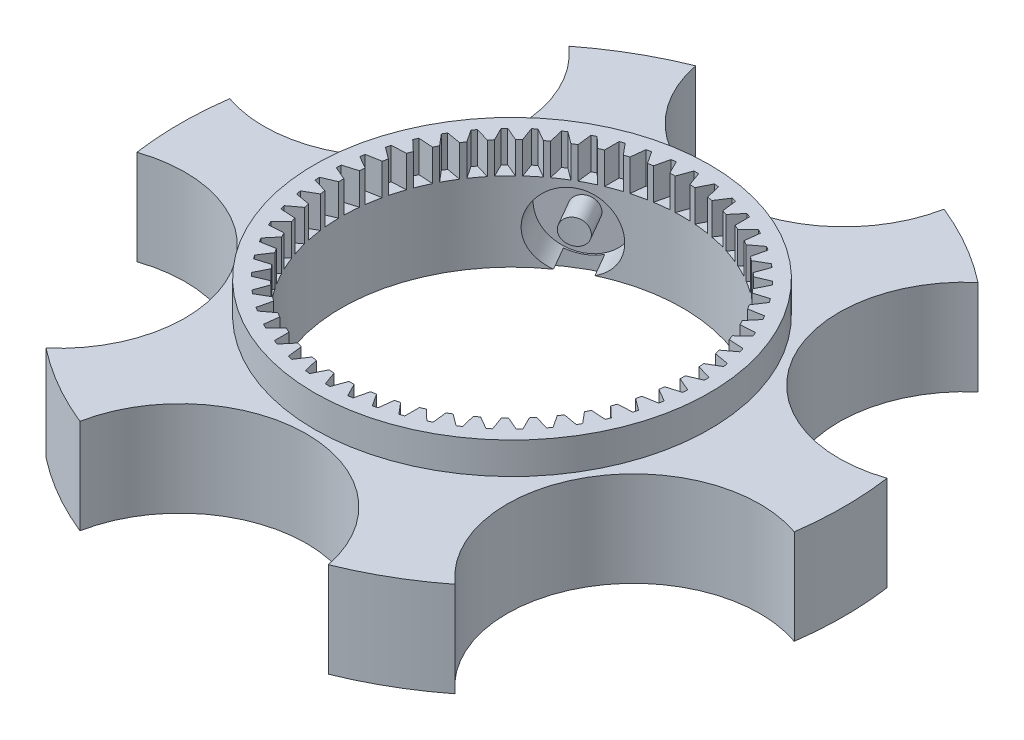
SolidWorks part; units mm, degrees
ref_plane "Plan de face" through (0, 0, 0) normal (0, 0, 1) x (1, 0, 0)
ref_plane "Plan de dessus" through (0, 0, 0) normal (0, 1, 0) x (1, 0, 0)
ref_plane "Plan de droite" through (0, 0, 0) normal (1, 0, 0) x (0, 0, -1)
sketch "Esquisse1" plane through (0, 0, 0) normal (0, 1, 0) x (1, 0, 0)
  arc A0 (64.7005, 82.6973) -> (39.2677, 97.381) centre (0, 0) ccw
  circle A4 centre (0, 105) radius 40 construction
  arc A5 (-39.2677, 97.381) -> (39.2677, 97.381) centre (0, 105) ccw
  arc A6 (64.7005, 82.6973) -> (103.9682, 14.6837) centre (90.9327, 52.5) ccw
  arc A7 (103.9682, -14.6837) -> (64.7005, -82.6973) centre (90.9327, -52.5) ccw
  arc A8 (39.2677, -97.381) -> (-39.2677, -97.381) centre (0, -105) ccw
  arc A9 (-64.7005, -82.6973) -> (-103.9682, -14.6837) centre (-90.9327, -52.5) ccw
  arc A10 (-103.9682, 14.6837) -> (-64.7005, 82.6973) centre (-90.9327, 52.5) ccw
  circle A11 centre (0, 0) radius 105 construction
  arc A12 (103.9682, -14.6837) -> (103.9682, 14.6837) centre (0, 0) ccw
  arc A13 (39.2677, -97.381) -> (64.7005, -82.6973) centre (0, 0) ccw
  arc A14 (-64.7005, -82.6973) -> (-39.2677, -97.381) centre (0, 0) ccw
  arc A15 (-103.9682, 14.6837) -> (-103.9682, -14.6837) centre (0, 0) ccw
  arc A16 (-39.2677, 97.381) -> (-64.7005, 82.6973) centre (0, 0) ccw
  dimension "D1" = 210
  dimension "D7" = 80
  dimension "D8" = 6
  dimension "D9" = 6
extrude "Boss.-Extru.1" add sketch "Esquisse1" along normal blind 30 contours A5 A16 A10 A15 A9 A14 A8 A13 A7 A12 A6 A0 region at (0, 0, 0)
sketch "Esquisse4" plane through (0, 30, 0) normal (0, 1, 0) x (1, 0, 0)
  circle A0 centre (0, 0) radius 54
  dimension "D1" = 108
extrude "Enlèv. mat.-Extru.1" cut sketch "Esquisse4" against normal through all
sketch "Esquisse5" plane through (0, 0, 0) normal (0, -1, 0) x (1, 0, 0)
  circle A0 centre (0, 0) radius 62.5
  dimension "D1" = 125
extrude "Enlèv. mat.-Extru.2" cut sketch "Esquisse5" against normal blind 5
sketch "Esquisse6" plane through (0, 30, 0) normal (0, 1, 0) x (1, 0, 0)
  line L0 (0, 0) -> (0, 58.3) construction
  line L1 (-3.6586, 56.05) -> (3.6586, 56.05) construction
  line L2 (0, 56.05) -> (-4.3653, 54.4612) construction
  line L3 (0.74, 58.2953) -> (2.3215, 53.9501)
  line L4 (-0.74, 58.2953) -> (-2.3215, 53.9501)
  line L5 (0.74, 58.2953) -> (-0.74, 58.2953) construction
  line L6 (6.0327, 57.987) -> (3.9574, 53.8548)
  line L7 (7.5027, 57.8152) -> (8.5691, 53.3158)
  line L8 (12.7238, 56.8946) -> (10.1828, 53.0312)
  line L9 (14.1639, 56.5533) -> (14.7007, 51.9605)
  line L10 (19.2428, 55.0328) -> (16.2705, 51.4905)
  line L11 (20.6335, 54.5266) -> (20.6335, 49.9025)
  line L12 (25.5016, 52.4267) -> (22.1382, 49.2534)
  line L13 (26.8242, 51.7625) -> (26.2873, 47.1696)
  line L14 (31.4155, 49.1117) -> (27.7064, 46.3503)
  line L15 (32.6521, 48.2984) -> (31.5857, 43.7989)
  line L16 (36.9046, 45.1325) -> (32.9, 42.8204)
  line L17 (38.0384, 44.1811) -> (36.4568, 39.8359)
  line L18 (41.8946, 40.5429) -> (37.6487, 38.7114)
  line L19 (42.9103, 39.4664) -> (40.835, 35.3342)
  line L20 (46.3181, 35.4051) -> (41.8883, 34.0789)
  line L21 (47.2019, 34.218) -> (44.6609, 30.3546)
  line L22 (50.1152, 29.7885) -> (45.5614, 28.9855)
  line L23 (50.8552, 28.5068) -> (47.8829, 24.9645)
  line L24 (53.2346, 23.7691) -> (48.6183, 23.5002)
  line L25 (53.8208, 22.4101) -> (50.4573, 19.2369)
  line L26 (55.6341, 17.4282) -> (51.0178, 17.6971)
  line L27 (56.0585, 16.0104) -> (52.3494, 13.2491)
  line L28 (57.2812, 10.8516) -> (52.7273, 11.6546)
  line L29 (57.5382, 9.3941) -> (53.5336, 7.0821)
  line L30 (58.1536, 4.1283) -> (53.7238, 5.4545)
  line L31 (58.2397, 2.6508) -> (53.9938, 0.8193)
  line L32 (58.2397, -2.6508) -> (53.9938, -0.8193)
  line L33 (58.1536, -4.1283) -> (53.7238, -5.4545)
  line L34 (57.5382, -9.3941) -> (53.5336, -7.0821)
  line L35 (57.2812, -10.8516) -> (52.7273, -11.6546)
  line L36 (56.0585, -16.0104) -> (52.3494, -13.2491)
  line L37 (55.6341, -17.4282) -> (51.0178, -17.6971)
  line L38 (53.8208, -22.4101) -> (50.4573, -19.2369)
  line L39 (53.2346, -23.7691) -> (48.6183, -23.5002)
  line L40 (50.8552, -28.5068) -> (47.8829, -24.9645)
  line L41 (50.1152, -29.7885) -> (45.5614, -28.9855)
  line L42 (47.2019, -34.218) -> (44.6609, -30.3546)
  line L43 (46.3181, -35.4051) -> (41.8883, -34.0789)
  line L44 (42.9103, -39.4664) -> (40.835, -35.3342)
  line L45 (41.8946, -40.5429) -> (37.6487, -38.7114)
  line L46 (38.0384, -44.1811) -> (36.4568, -39.8359)
  line L47 (36.9046, -45.1325) -> (32.9, -42.8204)
  line L48 (32.6521, -48.2984) -> (31.5857, -43.7989)
  line L49 (31.4155, -49.1117) -> (27.7064, -46.3503)
  line L50 (26.8242, -51.7625) -> (26.2873, -47.1696)
  line L51 (25.5016, -52.4267) -> (22.1382, -49.2534)
  line L52 (20.6335, -54.5266) -> (20.6335, -49.9025)
  line L53 (19.2428, -55.0328) -> (16.2705, -51.4905)
  line L54 (14.1639, -56.5533) -> (14.7007, -51.9605)
  line L55 (12.7238, -56.8946) -> (10.1828, -53.0312)
  line L56 (7.5027, -57.8152) -> (8.5691, -53.3158)
  line L57 (6.0327, -57.987) -> (3.9574, -53.8548)
  line L58 (0.74, -58.2953) -> (2.3215, -53.9501)
  line L59 (-0.74, -58.2953) -> (-2.3215, -53.9501)
  line L60 (-6.0327, -57.987) -> (-3.9574, -53.8548)
  line L61 (-7.5027, -57.8152) -> (-8.5691, -53.3158)
  line L62 (-12.7238, -56.8946) -> (-10.1828, -53.0312)
  line L63 (-14.1639, -56.5533) -> (-14.7007, -51.9605)
  line L64 (-19.2428, -55.0328) -> (-16.2705, -51.4905)
  line L65 (-20.6335, -54.5266) -> (-20.6335, -49.9025)
  line L66 (-25.5016, -52.4267) -> (-22.1382, -49.2534)
  line L67 (-26.8242, -51.7625) -> (-26.2873, -47.1696)
  line L68 (-31.4155, -49.1117) -> (-27.7064, -46.3503)
  line L69 (-32.6521, -48.2984) -> (-31.5857, -43.7989)
  line L70 (-36.9046, -45.1325) -> (-32.9, -42.8204)
  line L71 (-38.0384, -44.1811) -> (-36.4568, -39.8359)
  line L72 (-41.8946, -40.5429) -> (-37.6487, -38.7114)
  line L73 (-42.9103, -39.4664) -> (-40.835, -35.3342)
  line L74 (-46.3181, -35.4051) -> (-41.8883, -34.0789)
  line L75 (-47.2019, -34.218) -> (-44.6609, -30.3546)
  line L76 (-50.1152, -29.7885) -> (-45.5614, -28.9855)
  line L77 (-50.8552, -28.5068) -> (-47.8829, -24.9645)
  line L78 (-53.2346, -23.7691) -> (-48.6183, -23.5002)
  line L79 (-53.8208, -22.4101) -> (-50.4573, -19.2369)
  line L80 (-55.6341, -17.4282) -> (-51.0178, -17.6971)
  line L81 (-56.0585, -16.0104) -> (-52.3494, -13.2491)
  line L82 (-57.2812, -10.8516) -> (-52.7273, -11.6546)
  line L83 (-57.5382, -9.3941) -> (-53.5336, -7.0821)
  line L84 (-58.1536, -4.1283) -> (-53.7238, -5.4545)
  line L85 (-58.2397, -2.6508) -> (-53.9938, -0.8193)
  line L86 (-58.2397, 2.6508) -> (-53.9938, 0.8193)
  line L87 (-58.1536, 4.1283) -> (-53.7238, 5.4545)
  line L88 (-57.5382, 9.3941) -> (-53.5336, 7.0821)
  line L89 (-57.2812, 10.8516) -> (-52.7273, 11.6546)
  line L90 (-56.0585, 16.0104) -> (-52.3494, 13.2491)
  line L91 (-55.6341, 17.4282) -> (-51.0178, 17.6971)
  line L92 (-53.8208, 22.4101) -> (-50.4573, 19.2369)
  line L93 (-53.2346, 23.7691) -> (-48.6183, 23.5002)
  line L94 (-50.8552, 28.5068) -> (-47.8829, 24.9645)
  line L95 (-50.1152, 29.7885) -> (-45.5614, 28.9855)
  line L96 (-47.2019, 34.218) -> (-44.6609, 30.3546)
  line L97 (-46.3181, 35.4051) -> (-41.8883, 34.0789)
  line L98 (-42.9103, 39.4664) -> (-40.835, 35.3342)
  line L99 (-41.8946, 40.5429) -> (-37.6487, 38.7114)
  line L100 (-38.0384, 44.1811) -> (-36.4568, 39.8359)
  line L101 (-36.9046, 45.1325) -> (-32.9, 42.8204)
  line L102 (-32.6521, 48.2984) -> (-31.5857, 43.7989)
  line L103 (-31.4155, 49.1117) -> (-27.7064, 46.3503)
  line L104 (-26.8242, 51.7625) -> (-26.2873, 47.1696)
  line L105 (-25.5016, 52.4267) -> (-22.1382, 49.2534)
  line L106 (-20.6335, 54.5266) -> (-20.6335, 49.9025)
  line L107 (-19.2428, 55.0328) -> (-16.2705, 51.4905)
  line L108 (-14.1639, 56.5533) -> (-14.7007, 51.9605)
  line L109 (-12.7238, 56.8946) -> (-10.1828, 53.0312)
  line L110 (-7.5027, 57.8152) -> (-8.5691, 53.3158)
  line L111 (-6.0327, 57.987) -> (-3.9574, 53.8548)
  circle A0 centre (0, 0) radius 56.05 construction
  circle A1 centre (0, 0) radius 58.3 construction
  circle A2 centre (0, 0) radius 54 construction
  arc A3 (6.0327, 57.987) -> (7.5027, 57.8152) centre (0, 0) cw
  arc A4 (-0.74, 58.2953) -> (0.74, 58.2953) centre (0, 0) cw
  arc A5 (12.7238, 56.8946) -> (14.1639, 56.5533) centre (0, 0) cw
  arc A6 (19.2428, 55.0328) -> (20.6335, 54.5266) centre (0, 0) cw
  arc A7 (25.5016, 52.4267) -> (26.8242, 51.7625) centre (0, 0) cw
  arc A8 (31.4155, 49.1117) -> (32.6521, 48.2984) centre (0, 0) cw
  arc A9 (36.9046, 45.1325) -> (38.0384, 44.1811) centre (0, 0) cw
  arc A10 (41.8946, 40.5429) -> (42.9103, 39.4664) centre (0, 0) cw
  arc A11 (46.3181, 35.4051) -> (47.2019, 34.218) centre (0, 0) cw
  arc A12 (50.1152, 29.7885) -> (50.8552, 28.5068) centre (0, 0) cw
  arc A13 (53.2346, 23.7691) -> (53.8208, 22.4101) centre (0, 0) cw
  arc A14 (55.6341, 17.4282) -> (56.0585, 16.0104) centre (0, 0) cw
  arc A15 (57.2812, 10.8516) -> (57.5382, 9.3941) centre (0, 0) cw
  arc A16 (58.1536, 4.1283) -> (58.2397, 2.6508) centre (0, 0) cw
  arc A17 (58.2397, -2.6508) -> (58.1536, -4.1283) centre (0, 0) cw
  arc A18 (57.5382, -9.3941) -> (57.2812, -10.8516) centre (0, 0) cw
  arc A19 (56.0585, -16.0104) -> (55.6341, -17.4282) centre (0, 0) cw
  arc A20 (53.8208, -22.4101) -> (53.2346, -23.7691) centre (0, 0) cw
  arc A21 (50.8552, -28.5068) -> (50.1152, -29.7885) centre (0, 0) cw
  arc A22 (47.2019, -34.218) -> (46.3181, -35.4051) centre (0, 0) cw
  arc A23 (42.9103, -39.4664) -> (41.8946, -40.5429) centre (0, 0) cw
  arc A24 (38.0384, -44.1811) -> (36.9046, -45.1325) centre (0, 0) cw
  arc A25 (32.6521, -48.2984) -> (31.4155, -49.1117) centre (0, 0) cw
  arc A26 (26.8242, -51.7625) -> (25.5016, -52.4267) centre (0, 0) cw
  arc A27 (20.6335, -54.5266) -> (19.2428, -55.0328) centre (0, 0) cw
  arc A28 (14.1639, -56.5533) -> (12.7238, -56.8946) centre (0, 0) cw
  arc A29 (7.5027, -57.8152) -> (6.0327, -57.987) centre (0, 0) cw
  arc A30 (0.74, -58.2953) -> (-0.74, -58.2953) centre (0, 0) cw
  arc A31 (-6.0327, -57.987) -> (-7.5027, -57.8152) centre (0, 0) cw
  arc A32 (-12.7238, -56.8946) -> (-14.1639, -56.5533) centre (0, 0) cw
  arc A33 (-19.2428, -55.0328) -> (-20.6335, -54.5266) centre (0, 0) cw
  arc A34 (-25.5016, -52.4267) -> (-26.8242, -51.7625) centre (0, 0) cw
  arc A35 (-31.4155, -49.1117) -> (-32.6521, -48.2984) centre (0, 0) cw
  arc A36 (-36.9046, -45.1325) -> (-38.0384, -44.1811) centre (0, 0) cw
  arc A37 (-41.8946, -40.5429) -> (-42.9103, -39.4664) centre (0, 0) cw
  arc A38 (-46.3181, -35.4051) -> (-47.2019, -34.218) centre (0, 0) cw
  arc A39 (-50.1152, -29.7885) -> (-50.8552, -28.5068) centre (0, 0) cw
  arc A40 (-53.2346, -23.7691) -> (-53.8208, -22.4101) centre (0, 0) cw
  arc A41 (-55.6341, -17.4282) -> (-56.0585, -16.0104) centre (0, 0) cw
  arc A42 (-57.2812, -10.8516) -> (-57.5382, -9.3941) centre (0, 0) cw
  arc A43 (-58.1536, -4.1283) -> (-58.2397, -2.6508) centre (0, 0) cw
  arc A44 (-58.2397, 2.6508) -> (-58.1536, 4.1283) centre (0, 0) cw
  arc A45 (-57.5382, 9.3941) -> (-57.2812, 10.8516) centre (0, 0) cw
  arc A46 (-56.0585, 16.0104) -> (-55.6341, 17.4282) centre (0, 0) cw
  arc A47 (-53.8208, 22.4101) -> (-53.2346, 23.7691) centre (0, 0) cw
  arc A48 (-50.8552, 28.5068) -> (-50.1152, 29.7885) centre (0, 0) cw
  arc A49 (-47.2019, 34.218) -> (-46.3181, 35.4051) centre (0, 0) cw
  arc A50 (-42.9103, 39.4664) -> (-41.8946, 40.5429) centre (0, 0) cw
  arc A51 (-38.0384, 44.1811) -> (-36.9046, 45.1325) centre (0, 0) cw
  arc A52 (-32.6521, 48.2984) -> (-31.4155, 49.1117) centre (0, 0) cw
  arc A53 (-26.8242, 51.7625) -> (-25.5016, 52.4267) centre (0, 0) cw
  arc A54 (-20.6335, 54.5266) -> (-19.2428, 55.0328) centre (0, 0) cw
  arc A55 (-14.1639, 56.5533) -> (-12.7238, 56.8946) centre (0, 0) cw
  arc A56 (-7.5027, 57.8152) -> (-6.0327, 57.987) centre (0, 0) cw
  circle A57 centre (0, 0) radius 62.5
  arc A58 (8.5691, 53.3158) -> (10.1828, 53.0312) centre (0, 0) cw
  arc A59 (14.7007, 51.9605) -> (16.2705, 51.4905) centre (0, 0) cw
  arc A60 (20.6335, 49.9025) -> (22.1382, 49.2534) centre (0, 0) cw
  arc A61 (26.2873, 47.1696) -> (27.7064, 46.3503) centre (0, 0) cw
  arc A62 (31.5857, 43.7989) -> (32.9, 42.8204) centre (0, 0) cw
  arc A63 (36.4568, 39.8359) -> (37.6487, 38.7114) centre (0, 0) cw
  arc A64 (40.835, 35.3342) -> (41.8883, 34.0789) centre (0, 0) cw
  arc A65 (44.6609, 30.3546) -> (45.5614, 28.9855) centre (0, 0) cw
  arc A66 (47.8829, 24.9645) -> (48.6183, 23.5002) centre (0, 0) cw
  arc A67 (50.4573, 19.2369) -> (51.0178, 17.6971) centre (0, 0) cw
  arc A68 (52.3494, 13.2491) -> (52.7273, 11.6546) centre (0, 0) cw
  arc A69 (53.5336, 7.0821) -> (53.7238, 5.4545) centre (0, 0) cw
  arc A70 (53.9938, 0.8193) -> (53.9938, -0.8193) centre (0, 0) cw
  arc A71 (53.7238, -5.4545) -> (53.5336, -7.0821) centre (0, 0) cw
  arc A72 (52.7273, -11.6546) -> (52.3494, -13.2491) centre (0, 0) cw
  arc A73 (51.0178, -17.6971) -> (50.4573, -19.2369) centre (0, 0) cw
  arc A74 (48.6183, -23.5002) -> (47.8829, -24.9645) centre (0, 0) cw
  arc A75 (45.5614, -28.9855) -> (44.6609, -30.3546) centre (0, 0) cw
  arc A76 (41.8883, -34.0789) -> (40.835, -35.3342) centre (0, 0) cw
  arc A77 (37.6487, -38.7114) -> (36.4568, -39.8359) centre (0, 0) cw
  arc A78 (32.9, -42.8204) -> (31.5857, -43.7989) centre (0, 0) cw
  arc A79 (27.7064, -46.3503) -> (26.2873, -47.1696) centre (0, 0) cw
  arc A80 (22.1382, -49.2534) -> (20.6335, -49.9025) centre (0, 0) cw
  arc A81 (16.2705, -51.4905) -> (14.7007, -51.9605) centre (0, 0) cw
  arc A82 (10.1828, -53.0312) -> (8.5691, -53.3158) centre (0, 0) cw
  arc A83 (3.9574, -53.8548) -> (2.3215, -53.9501) centre (0, 0) cw
  arc A84 (-2.3215, -53.9501) -> (-3.9574, -53.8548) centre (0, 0) cw
  arc A85 (-8.5691, -53.3158) -> (-10.1828, -53.0312) centre (0, 0) cw
  arc A86 (-14.7007, -51.9605) -> (-16.2705, -51.4905) centre (0, 0) cw
  arc A87 (-20.6335, -49.9025) -> (-22.1382, -49.2534) centre (0, 0) cw
  arc A88 (-26.2873, -47.1696) -> (-27.7064, -46.3503) centre (0, 0) cw
  arc A89 (-31.5857, -43.7989) -> (-32.9, -42.8204) centre (0, 0) cw
  arc A90 (-36.4568, -39.8359) -> (-37.6487, -38.7114) centre (0, 0) cw
  arc A91 (-40.835, -35.3342) -> (-41.8883, -34.0789) centre (0, 0) cw
  arc A92 (-44.6609, -30.3546) -> (-45.5614, -28.9855) centre (0, 0) cw
  arc A93 (-47.8829, -24.9645) -> (-48.6183, -23.5002) centre (0, 0) cw
  arc A94 (-50.4573, -19.2369) -> (-51.0178, -17.6971) centre (0, 0) cw
  arc A95 (-52.3494, -13.2491) -> (-52.7273, -11.6546) centre (0, 0) cw
  arc A96 (-53.5336, -7.0821) -> (-53.7238, -5.4545) centre (0, 0) cw
  arc A97 (-53.9938, -0.8193) -> (-53.9938, 0.8193) centre (0, 0) cw
  arc A98 (-53.7238, 5.4545) -> (-53.5336, 7.0821) centre (0, 0) cw
  arc A99 (-52.7273, 11.6546) -> (-52.3494, 13.2491) centre (0, 0) cw
  arc A100 (-51.0178, 17.6971) -> (-50.4573, 19.2369) centre (0, 0) cw
  arc A101 (-48.6183, 23.5002) -> (-47.8829, 24.9645) centre (0, 0) cw
  arc A102 (-45.5614, 28.9855) -> (-44.6609, 30.3546) centre (0, 0) cw
  arc A103 (-41.8883, 34.0789) -> (-40.835, 35.3342) centre (0, 0) cw
  arc A104 (-37.6487, 38.7114) -> (-36.4568, 39.8359) centre (0, 0) cw
  arc A105 (-32.9, 42.8204) -> (-31.5857, 43.7989) centre (0, 0) cw
  arc A106 (-27.7064, 46.3503) -> (-26.2873, 47.1696) centre (0, 0) cw
  arc A107 (-22.1382, 49.2534) -> (-20.6335, 49.9025) centre (0, 0) cw
  arc A108 (-16.2705, 51.4905) -> (-14.7007, 51.9605) centre (0, 0) cw
  arc A109 (-10.1828, 53.0312) -> (-8.5691, 53.3158) centre (0, 0) cw
  arc A110 (-3.9574, 53.8548) -> (-2.3215, 53.9501) centre (0, 0) cw
  arc A111 (2.3215, 53.9501) -> (3.9574, 53.8548) centre (0, 0) cw
  point P9 (0, 56.05)
  point P231 (0, 0)
  point P339 (0, 0)
  dimension "D1" = 112.1
  dimension "D2" = 116.6
  dimension "D4" = 108
  dimension "D7" = 125
  dimension "D3" = 20
  dimension "D5" = 1.48
  dimension "D6" = 54
  dimension "D8" = 54
extrude "Boss.-Extru.2" add sketch "Esquisse6" along normal blind 10
sketch "Esquisse7" plane through (0, 30, 0) normal (0, 1, 0) x (1, 0, 0)
  line L0 (0, 0) -> (-52.5, 90.9327) construction
  arc A0 (-39.2677, 97.381) -> (-64.7005, 82.6973) centre (0, 0) ccw construction
ref_plane "Plan1" through (-27, 0, -46.7654) normal (0.5, 0, 0.866) x (0.866, 0, -0.5)
ref_plane "Plan2" through (-22, 0, -38.1051) normal (0.5, 0, 0.866) x (0.866, 0, -0.5)
sketch "Esquisse8" plane through (-22, 0, -38.1051) normal (0.5, 0, 0.866) x (0.866, 0, -0.5)
  line L0 (0, 0) -> (0, 42.8538) construction
  line L1 (12.5, 0) -> (82.6973, 0) construction
  circle A0 centre (0, 16) radius 12
  circle A1 centre (0, 16) radius 3.95
  dimension "D1" = 24
  dimension "D2" = 7.9
  dimension "D3" = 16
extrude "Enlèv. mat.-Extru.3" cut sketch "Esquisse8" against normal blind 19
ref_axis "Axe1" through (0, 44.9965, 0) along (0, -1, 0)
pattern_circular "Répétition circulaire1" count 3 over 360 about axis through (0, 44.9965, 0) along (0, -1, 0) of "Enlèv. mat.-Extru.3"
sketch "Esquisse9" plane through (0, 30, 0) normal (0, 1, 0) x (1, 0, 0)
  circle A0 centre (90.9327, -52.5) radius 40
  circle A1 centre (90.9327, 52.5) radius 40
  circle A2 centre (0, 105) radius 40
  circle A3 centre (0, -105) radius 40
  circle A4 centre (-90.9327, -52.5) radius 40
  circle A5 centre (-90.9327, 52.5) radius 40
  circle A6 centre (0, 0) radius 145
